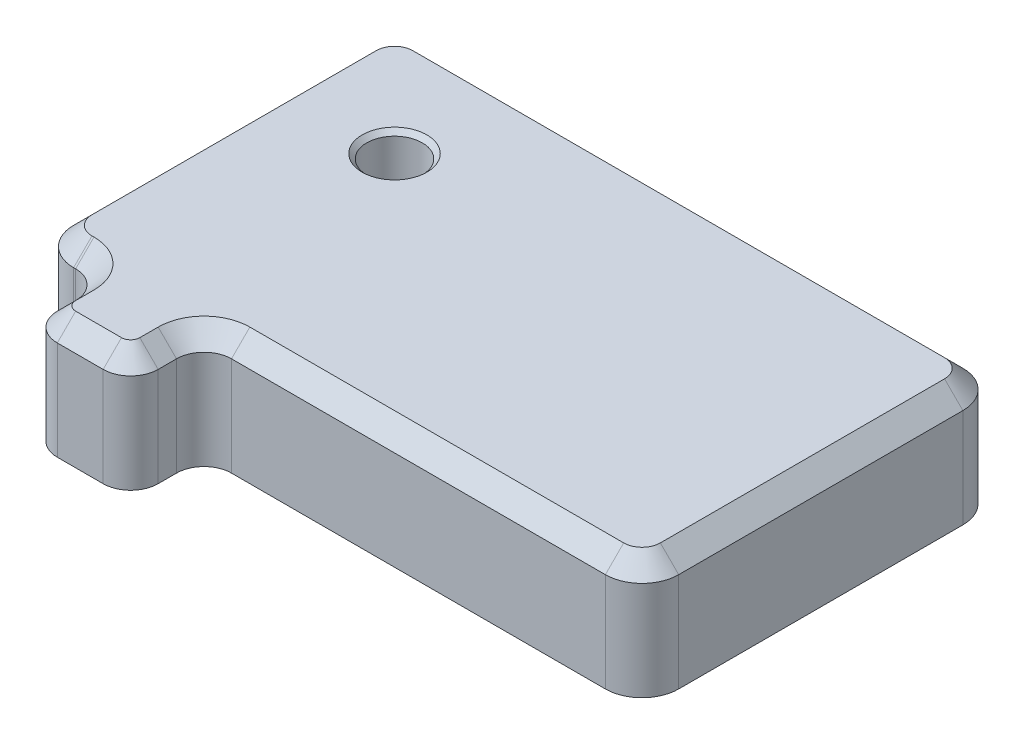
SolidWorks part; units mm, degrees
ref_plane "Front Plane" through (0, 0, 0) normal (0, 0, 1) x (1, 0, 0)
ref_plane "Top Plane" through (0, 0, 0) normal (0, 1, 0) x (1, 0, 0)
ref_plane "Right Plane" through (0, 0, 0) normal (1, 0, 0) x (0, 0, -1)
sketch "Sketch1" plane through (0, 0, 0) normal (0, 1, 0) x (1, 0, 0)
  line L1 (-25, 11.5) -> (25, 11.5)
  line L2 (-25, 11.5) -> (-25, -11.5)
  line L3 (-25, -11.5) -> (25, -11.5)
  line L4 (25, 11.5) -> (25, -11.5)
  line L5 (-25, 11.5) -> (25, -11.5) construction
  line L6 (-25, -11.5) -> (25, 11.5) construction
  circle A0 centre (20.28, 6.78) radius 3.03
  point P0 (0, 0)
  dimension "D3" = 6.06
  dimension "D1" = 50
  dimension "D2" = 23
  dimension "D4" = 4.72
  dimension "D5" = 4.72
extrude "Boss-Extrude1" add sketch "Sketch1" along normal blind 1.6
sketch "Sketch2" plane through (0, 1.6, 0) normal (0, 1, 0) x (1, 0, 0)
  line L0 (16.28, 13.5) -> (16.28, 11.55) construction
  line L1 (24.28, 13.5) -> (24.28, 11.55) construction
  line L2 (-33, 19.5) -> (-33, -19.5)
  line L3 (-33, -19.5) -> (33, -19.5)
  line L4 (20.28, 19.5) -> (20.28, -13.5) construction
  line L5 (16.28, -11.55) -> (16.28, -13.5) construction
  line L6 (24.28, -11.55) -> (24.28, -13.5) construction
  line L7 (33, -19.5) -> (33, 19.5)
  line L8 (27, -13.5) -> (27, 13.5)
  line L9 (27, 13.5) -> (-27, 13.5)
  line L10 (-27, 13.5) -> (-27, -13.5)
  line L11 (-27, -13.5) -> (27, -13.5)
  line L12 (27, -13.5) -> (27, -10.78)
  line L13 (27, 13.5) -> (24.28, 13.5)
  line L14 (-27, 13.5) -> (-27, -13.5)
  line L15 (-27, -13.5) -> (16.28, -13.5)
  line L16 (33, 19.5) -> (-33, 19.5)
  line L25 (24.28, -13.5) -> (27, -13.5)
  line L26 (-27, -13.5) -> (27, -13.5) construction
  line L27 (16.28, 13.5) -> (-27, 13.5)
  line L28 (27, 13.5) -> (-27, 13.5) construction
  line L29 (16.28, -11.55) -> (24.28, -11.55) construction
  line L30 (-25, -11.5) -> (25, -11.5) construction
  line L31 (16.28, 11.55) -> (24.28, 11.55) construction
  line L32 (25, 11.5) -> (-25, 11.5) construction
  line L33 (27, -2.78) -> (25.05, -2.78) construction
  line L34 (25.05, -2.78) -> (25.05, -10.78) construction
  line L35 (25.05, -10.78) -> (27, -10.78) construction
  line L36 (25, -11.5) -> (25, 11.5) construction
  line L37 (27, -2.78) -> (27, 13.5)
  line L38 (27, -13.5) -> (27, 13.5) construction
  line L39 (24.28, -13.5) -> (16.28, -13.5)
  line L40 (24.28, 13.5) -> (16.28, 13.5)
  line L41 (27, -2.78) -> (27, -10.78)
  circle A0 centre (20.28, 6.78) radius 3.03 construction
  circle A1 centre (20.28, 6.78) radius 3.03 construction
  dimension "D2" = 0.05
  dimension "D3" = 4
  dimension "D4" = 4
  dimension "D6" = 0.05
  dimension "D7" = 0.05
  dimension "D1" = 2
  dimension "D5" = 6
extrude "Boss-Extrude2" add sketch "Sketch2" against normal offset from surface 0.8 and the other way blind 10 separate body up to face at (0, 0, 0)
sketch "Sketch3" plane through (0, 11.6, 0) normal (0, 1, 0) x (1, 0, 0)
  line L4 (33, 19.5) -> (-33, 19.5)
  line L5 (-33, 19.5) -> (-33, -19.5)
  line L6 (-33, -19.5) -> (33, -19.5)
  line L7 (33, -19.5) -> (33, 19.5)
  line L8 (33, 19.5) -> (-33, 19.5)
  line L9 (-33, 19.5) -> (-33, -19.5)
  line L10 (-33, -19.5) -> (33, -19.5)
  line L11 (33, -19.5) -> (33, 19.5)
  dimension "D1" = 0
extrude "Boss-Extrude3" add sketch "Sketch3" along normal blind 2
sketch "Sketch5" plane through (0, 11.6, 0) normal (0, -1, 0) x (1, 0, 0)
  line L0 (-15.51, -2.01) -> (-25.05, -2.01)
  line L7 (-15.51, -2.01) -> (-15.51, -11.55)
  line L8 (-15.51, -11.55) -> (-25.05, -11.55)
  line L9 (-25.05, -2.01) -> (-25.05, -11.55)
  line L10 (-15.51, -2.01) -> (-25.05, -11.55) construction
  line L11 (-15.51, -11.55) -> (-25.05, -2.01) construction
  line L14 (-27, 13.5) -> (-27, -13.5) construction
  line L15 (-27, -13.5) -> (27, -13.5) construction
  circle A2 centre (-20.28, -6.78) radius 3.03 construction
  dimension "D2" = 9.54
  dimension "D4" = 6.72
  dimension "D5" = 6.72
fillet "Fillet1" radius 4 4 edges at (33, 7.2, 19.5) (33, 7.2, -19.5) (-33, 7.2, 19.5) (-33, 7.2, -19.5)
fillet "Fillet2" radius 1 4 edges at (-27, 6.2, -13.5) (-27, 6.2, 13.5) (27, 6.2, 13.5) (27, 6.2, -13.5)
fillet "Fillet5" radius 1 8 edges at (26.7071, 11.6, 13.2071) (27, 11.6, 0) (26.7071, 11.6, -13.2071) (0, 11.6, -13.5) (-26.7071, 11.6, -13.2071) (-27, 11.6, 0) (-26.7071, 11.6, 13.2071) (0, 11.6, 13.5)
ref_plane "Plane1" through (0, 0, 0) normal (1, 0, 0) x (0, 0, -1)
sketch "Sketch15" plane through (0, 0.8, 0) normal (0, -1, 0) x (1, 0, 0)
  line L32 (26, 18.5) -> (-26, 18.5)
  line L33 (-32, 12.5) -> (-32, -12.5)
  line L34 (-26, -18.5) -> (26, -18.5)
  line L35 (32, -12.5) -> (32, 12.5)
  line L36 (-28, 12.5) -> (-28, -12.5)
  line L37 (-26, -14.5) -> (26, -14.5)
  line L38 (28, -12.5) -> (28, 12.5)
  line L39 (26, 14.5) -> (-26, 14.5)
  line L40 (-28, 12.5) -> (-28, -12.5)
  line L41 (-26, -14.5) -> (26, -14.5)
  line L42 (28, -12.5) -> (28, 12.5)
  line L43 (26, 14.5) -> (-26, 14.5)
  arc A24 (-26, 18.5) -> (-32, 12.5) centre (-26, 12.5) ccw
  arc A25 (-32, -12.5) -> (-26, -18.5) centre (-26, -12.5) ccw
  arc A26 (26, -18.5) -> (32, -12.5) centre (26, -12.5) ccw
  arc A27 (32, 12.5) -> (26, 18.5) centre (26, 12.5) ccw
  arc A28 (-26, 14.5) -> (-28, 12.5) centre (-26, 12.5) ccw
  arc A29 (-28, -12.5) -> (-26, -14.5) centre (-26, -12.5) ccw
  arc A30 (26, -14.5) -> (28, -12.5) centre (26, -12.5) ccw
  arc A31 (28, 12.5) -> (26, 14.5) centre (26, 12.5) ccw
  arc A32 (-26, 14.5) -> (-28, 12.5) centre (-26, 12.5) ccw
  arc A33 (-28, -12.5) -> (-26, -14.5) centre (-26, -12.5) ccw
  arc A34 (26, -14.5) -> (28, -12.5) centre (26, -12.5) ccw
  arc A35 (28, 12.5) -> (26, 14.5) centre (26, 12.5) ccw
  dimension "D1" = 1
  dimension "D2" = 4
extrude "Cut-Extrude2" cut sketch "Sketch15" against normal blind 2
extrude "Boss-Extrude4" add sketch "Sketch5" along normal blind 8 contours L0 L9 L8 L7 region at (-20.28, 11.6, -6.78)
sketch "Sketch14" plane through (0, 3.6, 0) normal (0, -1, 0) x (1, 0, 0)
  line L1 (26, -13.5) -> (-26, -13.5) construction
  line L6 (-27, 12.5) -> (-27, -12.5) construction
  circle A0 centre (-20.28, -6.78) radius 3.03
  dimension "D1" = 6.06
  dimension "D2" = 6.72
  dimension "D3" = 6.72
extrude "Cut-Extrude3" cut sketch "Sketch14" against normal through all
fillet "Fillet6" radius 2 4 edges at (-25.05, 7.6, -11.55) (-25.05, 7.6, -2.01) (-15.51, 7.6, -11.55) (-15.51, 7.6, -2.01)
fillet "Fillet7" radius 1 14 edges at (-24.4642, 3.6, -2.5958) (-20.28, 3.6, -2.01) (-16.0958, 3.6, -2.5958) (-15.51, 3.6, -6.78) (-16.0958, 3.6, -10.9642) (-20.28, 3.6, -11.55) (-24.4642, 3.6, -10.9642) (-25.05, 3.6, -6.78) (-24.4642, 11.6, -2.5958) (-20.28, 11.6, -2.01) (-24.4642, 11.6, -10.9642) (-16.0958, 11.6, -10.9642) (-16.0958, 11.6, -2.5958) (-15.51, 11.6, -6.78)
chamfer "Chamfer2" distance 0.5 angle 45 2 edges at (-20.28, 3.6, -9.81) (-20.28, 13.6, -9.81)
sketch "Sketch18" plane through (0, 0, 19.5) normal (0, 0, 1) x (1, 0, 0)
  line L0 (-29, 13.6) -> (29, 13.6) construction
  line L1 (-25.78, 13.6) -> (-14.78, 13.6)
  line L2 (-25.78, 13.6) -> (-25.78, 0.8)
  line L3 (-25.78, 0.8) -> (-14.78, 0.8)
  line L4 (-14.78, 13.6) -> (-14.78, 0.8)
  line L5 (29, 0.8) -> (-29, 0.8) construction
  line L6 (-29, 13.6) -> (-29, 0.8) construction
  dimension "D1" = 11
  dimension "D2" = 3.22
extrude "Boss-Extrude6" add sketch "Sketch18" along normal blind 8
fillet "Fillet8" radius 3 4 edges at (-14.78, 7.2, 19.5) (-25.78, 7.2, 19.5) (-14.78, 7.2, 27.5) (-25.78, 7.2, 27.5)
chamfer "Chamfer4" distance 2 angle 45 16 edges at (-28.89, 13.6, 19.5) (-26.6587, 13.6, 20.3787) (-31.8284, 13.6, 18.3284) (-25.78, 13.6, 23.5) (-33, 13.6, 0) (-24.9013, 13.6, 26.6213) (-31.8284, 13.6, -18.3284) (-20.28, 13.6, 27.5) (0, 13.6, -19.5) (-15.6587, 13.6, 26.6213) (31.8284, 13.6, -18.3284) (-14.78, 13.6, 23.5) (33, 13.6, 0) (-13.9013, 13.6, 20.3787) (31.8284, 13.6, 18.3284) (8.61, 13.6, 19.5)
sketch "Sketch19" plane through (0, 13.6, 0) normal (0, 1, 0) x (1, 0, 0)
  line L0 (-31, 0) -> (-37, 0) construction
  line L1 (-31, 15.5) -> (-31, -15.5) construction
  line L2 (-55, 0) -> (55, 0) construction
sketch "Sketch20" plane through (0, 0, 27.5) normal (0, 0, 1) x (1, 0, 0)
  circle A0 centre (-40.2784, 6.2) radius 2.85
  dimension "D1" = 5.7
extrude "Cut-Extrude4" cut sketch "Sketch20" against normal up to next contours A0 rebuild error yes
chamfer "Chamfer5" distance 0.5 angle 45 rebuild error yes
sketch "Sketch21" plane through (0, 0, -19.5) normal (0, 0, -1) x (-1, 0, 0)
  line L1 (-0.4028, 8.3848) -> (8.5372, 8.3848)
  line L2 (-0.4028, 8.3848) -> (-0.4028, 5.1248)
  line L3 (-0.4028, 5.1248) -> (8.5372, 5.1248)
  line L4 (8.5372, 8.3848) -> (8.5372, 5.1248)
  dimension "D1" = 8.94
  dimension "D2" = 3.26
extrude "Cut-Extrude5" cut sketch "Sketch21" against normal up to surface (6 mm away) up to face at (0, 5.7, -13.5)
fillet "Fillet9" radius 1 12 edges at (-4.0672, 5.1248, -13.5) (-4.0672, 5.1248, -19.5) (-8.5372, 6.7548, -13.5) (-8.5372, 6.7548, -19.5) (-8.5372, 5.1248, -16.5) (-4.0672, 8.3848, -13.5) (-4.0672, 8.3848, -19.5) (-8.5372, 8.3848, -16.5) (0.4028, 6.7548, -13.5) (0.4028, 5.1248, -16.5) (0.4028, 6.7548, -19.5) (0.4028, 8.3848, -16.5)
